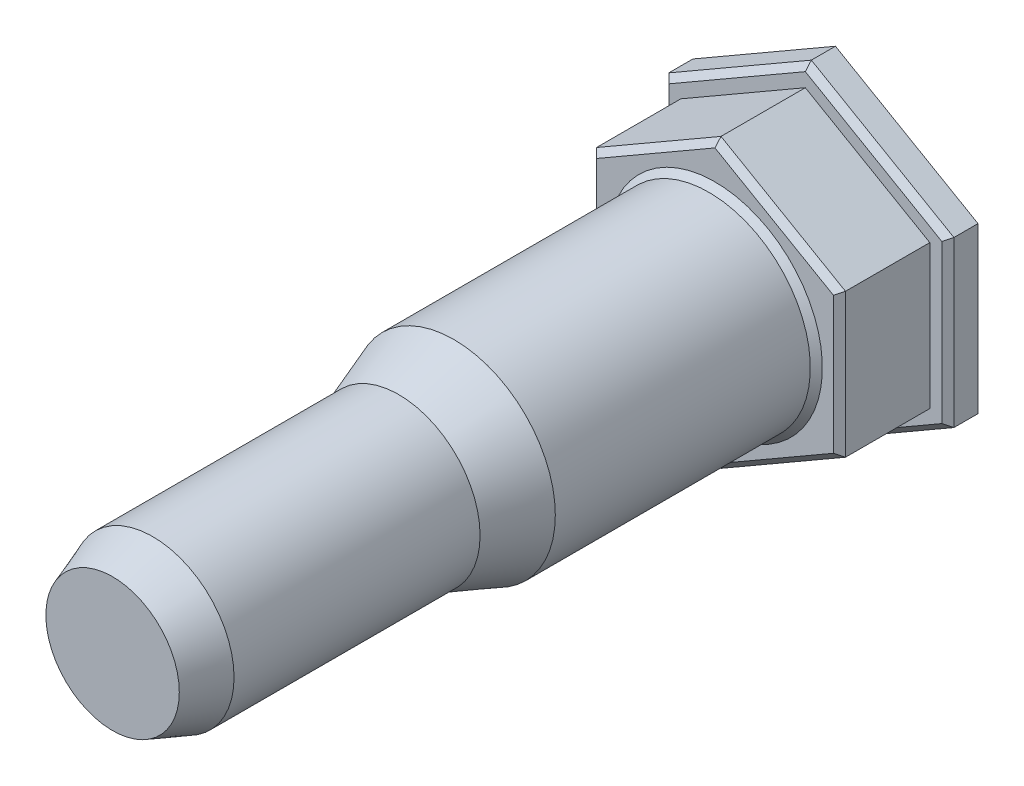
SolidWorks part; units mm, degrees
ref_plane "Front Plane" through (0, 0, 0) normal (0, 0, 1) x (1, 0, 0)
ref_plane "Top Plane" through (0, 0, 0) normal (0, 1, 0) x (1, 0, 0)
ref_plane "Right Plane" through (0, 0, 0) normal (1, 0, 0) x (0, 0, -1)
sketch "Sketch1" plane through (0, 0, 0) normal (0, 0, 1) x (1, 0, 0)
  line L12 (0, 7.1591) -> (6.2, 3.5796)
  line L14 (6.2, 3.5796) -> (6.2, -3.5796)
  line L15 (6.2, -3.5796) -> (0, -7.1591)
  line L16 (0, -7.1591) -> (-6.2, -3.5796)
  line L17 (-6.2, -3.5796) -> (-6.2, 3.5796)
  line L18 (-6.2, 3.5796) -> (0, 7.1591)
  line L19 (-7.1, 4.0992) -> (0, 8.1984)
  line L20 (0, 8.1984) -> (7.1, 4.0992)
  line L21 (7.1, 4.0992) -> (7.1, -4.0992)
  line L22 (7.1, -4.0992) -> (0, -8.1984)
  line L23 (0, -8.1984) -> (-7.1, -4.0992)
  line L24 (-7.1, -4.0992) -> (-7.1, 4.0992)
  circle A1 centre (0, 0) radius 3.05
  circle A2 centre (0, 0) radius 5.05
  circle A3 centre (0, 0) radius 2
  circle A4 centre (0, 0) radius 4.05
  point P3 (0, 7.1591)
  point P4 (6.2, 3.5796)
  point P7 (6.2, -3.5796)
  point P9 (0, -7.1591)
  point P10 (-6.2, -3.5796)
  point P12 (-6.2, 3.5796)
  point P13 (0, 0)
  dimension "D1" = 12.4
  dimension "D6" = 6.1
  dimension "D7" = 10.1
  dimension "D8" = 4
  dimension "D9" = 8.1
  dimension "D2" = 6
  dimension "D3" = 120
  dimension "D4" = 120
  dimension "D5" = 0.9
extrude "Boss-Extrude1" add sketch "Sketch1" along normal blind 1.5 contours L19 L20 L21 L22 L23 L24
ref_plane "Plane1" through (-7.1, -4.0992, 0) normal (-0.866, 0.5, 0) x (0, 0, 1)
ref_plane "Plane2" through (0, -8.1984, 0) normal (-0.866, 0.5, 0) x (0, 0, 1)
extrude "Boss-Extrude3" add sketch "Sketch1<8>" along normal blind 36 contours A4
sketch "Sketch1<8>" plane through (0, 0, 0) normal (0, 0, 1) x (1, 0, 0) same geometry as "Sketch1"
extrude "Boss-Extrude4" add sketch "Sketch1<9>" along normal blind 19 contours A2
sketch "Sketch1<9>" plane through (0, 0, 0) normal (0, 0, 1) x (1, 0, 0) same geometry as "Sketch1"
shell "Shell1" thickness 2
extrude "Cut-Extrude1" cut sketch "Sketch1<10>" along normal blind 11 contours A1
sketch "Sketch1<10>" plane through (0, 0, 0) normal (0, 0, 1) x (1, 0, 0) same geometry as "Sketch1"
extrude "Boss-Extrude2" add sketch "Sketch1<3>" along normal blind 6 contours L17 L18 L12 L14 L15 L16 | A1
sketch "Sketch1<3>" plane through (0, 0, 0) normal (0, 0, 1) x (1, 0, 0) same geometry as "Sketch1"
chamfer "Chamfer1" distance 2 angle 20 1 edges at (4.05, 0, 36) first distance on face at (4.05, 0, 19)
chamfer "Chamfer2" distance 1 angle 70 1 edges at (4.05, 0, 19) first distance on face at (4.05, 0, 19)
chamfer "Chamfer3" distance 0.6 angle 60 1 edges at (2.05, 0, 17) first distance on face at (2.05, 0, 17)
chamfer "Chamfer5" distance 0.3 angle 45 13 edges at (-5.05, 0, 6) (-6.2, 0, 6) (-3.1, 5.3694, 6) (3.1, 5.3694, 6) (6.2, 0, 6) (3.1, -5.3694, 6) (-3.1, -5.3694, 6) (7.1, 0, 1.5) (3.55, -6.1488, 1.5) (-3.55, -6.1488, 1.5) (-7.1, 0, 1.5) (3.55, 6.1488, 1.5) (-3.55, 6.1488, 1.5)
